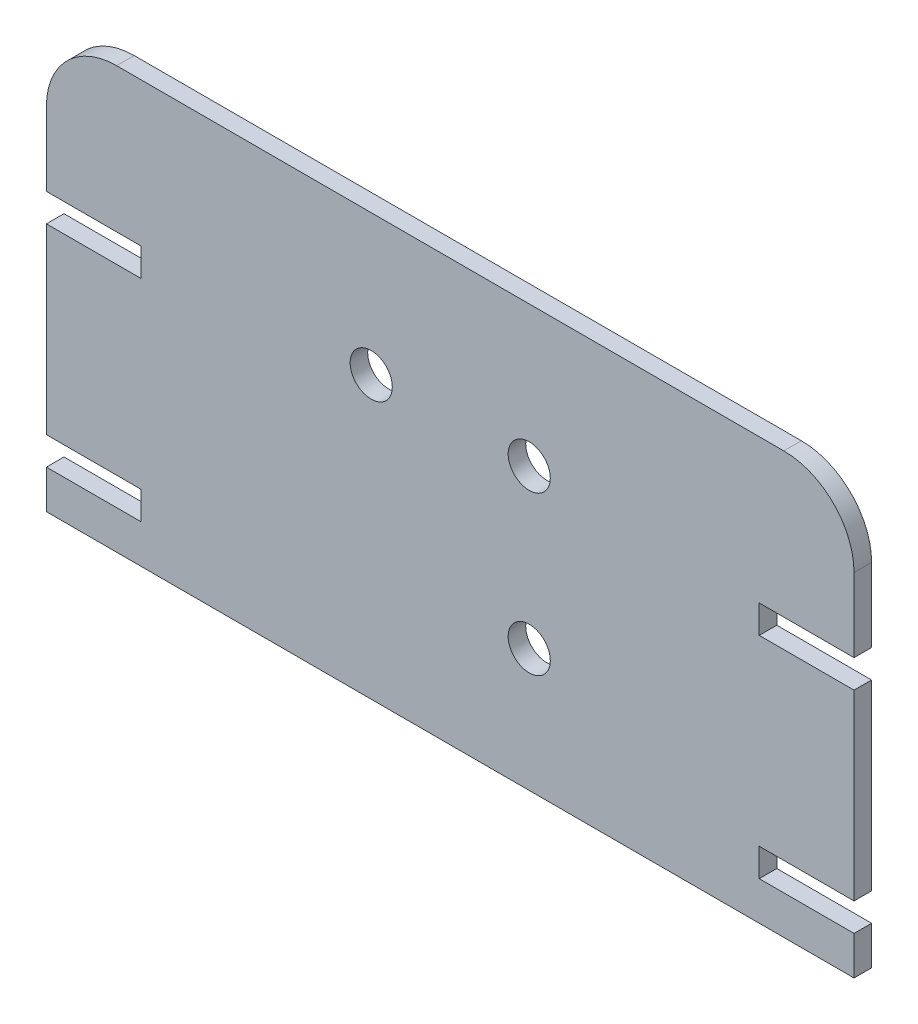
SolidWorks part; units mm, degrees
ref_plane "Front Plane" through (0, 0, 0) normal (0, 0, 1) x (1, 0, 0)
ref_plane "Top Plane" through (0, 0, 0) normal (0, 1, 0) x (1, 0, 0)
ref_plane "Right Plane" through (0, 0, 0) normal (1, 0, 0) x (0, 0, -1)
sketch "Sketch1" plane through (0, 0, 0) normal (0, 0, 1) x (1, 0, 0)
  line L1 (-115, -60) -> (115, -60)
  line L2 (-115, -60) -> (-115, 60)
  line L3 (-115, 60) -> (115, 60)
  line L4 (115, -60) -> (115, 60)
  line L5 (-115, -60) -> (115, 60) construction
  line L6 (-115, 60) -> (115, -60) construction
  point P0 (0, 0)
  dimension "D1" = 230
  dimension "D2" = 120
extrude "Boss-Extrude1" add sketch "Sketch1" along normal blind 5
sketch "Sketch2" plane through (0, 0, 0) normal (0, 0, -1) x (-1, 0, 0)
  line L0 (115, 11) -> (88, 11)
  line L1 (115, 60) -> (115, -60) construction
  line L2 (88, 11) -> (88, 19)
  line L3 (88, 19) -> (115, 19)
  line L4 (115, 19) -> (115, 11)
  line L5 (117.8, 19) -> (115.5, 19) construction
  line L6 (115.5, 11) -> (117.8, 11) construction
  line L7 (115, -49) -> (88, -49)
  line L8 (88, -41) -> (115, -41)
  line L9 (88, -49) -> (88, -41)
  line L10 (115, -41) -> (115, -49)
  line L11 (115.5, -49) -> (117.8, -49) construction
  line L12 (117.8, -41) -> (115.5, -41) construction
  line L13 (115, -40.5) -> (115, -30.5) construction
  line L14 (0, 2.75) -> (0, -2.75) construction
  line L15 (-115, -41) -> (-115, -49)
  line L16 (-88, -49) -> (-88, -41)
  line L17 (-88, -41) -> (-115, -41)
  line L18 (-115, -49) -> (-88, -49)
  line L19 (-115, 19) -> (-115, 11)
  line L20 (-88, 19) -> (-115, 19)
  line L21 (-88, 11) -> (-88, 19)
  line L22 (-115, 11) -> (-88, 11)
  dimension "D1" = 27
  dimension "D2" = 27
extrude "Cut-Extrude1" cut sketch "Sketch2" against normal up to next
sketch "Sketch3" plane through (0, 0, 5) normal (0, 0, 1) x (1, 0, 0)
  line L0 (-115, 20) -> (115, 20) construction
  line L1 (-115, 60) -> (-115, 19) construction
  line L2 (115, 19) -> (115, 60) construction
  line L3 (115, 60) -> (-115, 60) construction
  line L4 (22.5, 60) -> (22.5, -60) construction
  line L5 (-115, -60) -> (115, -60) construction
  circle A0 centre (22.5, 20) radius 6
  circle A1 centre (-22.5, 20) radius 6
  circle A2 centre (22.5, -25) radius 6
  dimension "D2" = 12
  dimension "D3" = 45
  dimension "D1" = 40
  dimension "D4" = 45
  dimension "D5" = 22.5
extrude "Cut-Extrude2" cut sketch "Sketch3" against normal up to next
fillet "Fillet1" radius 20 2 edges at (115, 60, 2.5) (-115, 60, 2.5)
